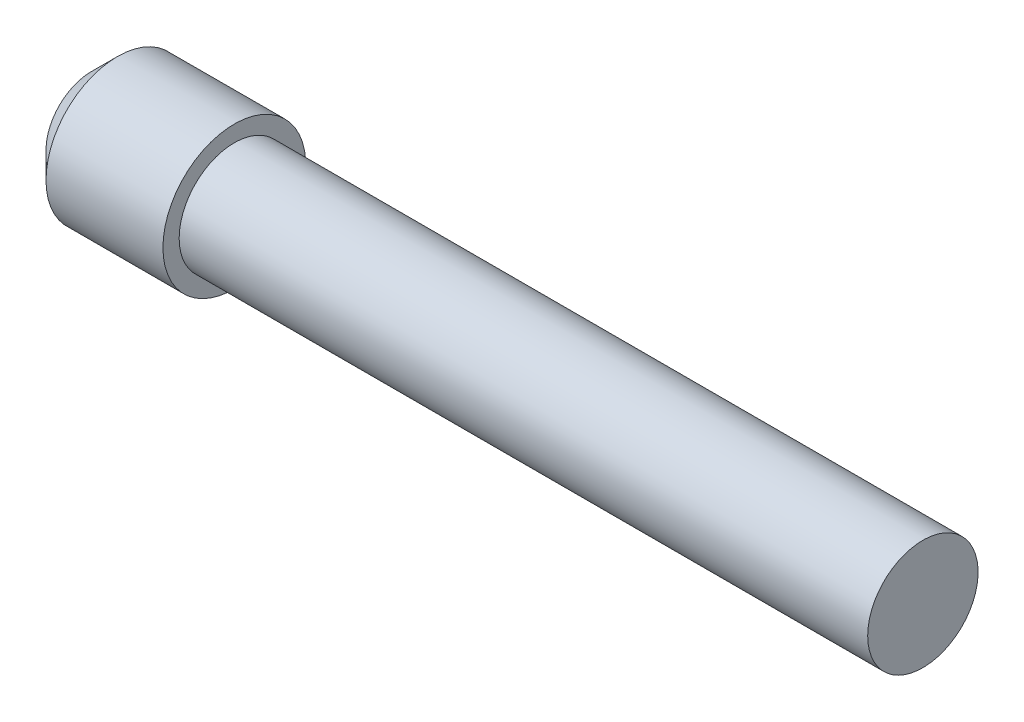
SolidWorks part; units mm, degrees
ref_plane "Front Plane" through (0, 0, 0) normal (0, 0, 1) x (1, 0, 0)
ref_plane "Top Plane" through (0, 0, 0) normal (0, 1, 0) x (1, 0, 0)
ref_plane "Right Plane" through (0, 0, 0) normal (1, 0, 0) x (0, 0, -1)
sketch "Sketch1" plane through (0, 0, 0) normal (0, 0, 1) x (1, 0, 0)
  line L0 (-9.4589, 0) -> (1.0894, 0) construction
  line L1 (0, 2.75) -> (-5.5, 2.75)
  line L2 (-5.5, 2.75) -> (-5.5, 0)
  line L3 (-5.5, 0) -> (26.5, 0)
  line L4 (0, 2.75) -> (0, 2.125)
  line L5 (0, 2.125) -> (0, 0) construction
  line L6 (0, 2.125) -> (26.5, 2.125)
  line L7 (26.5, 2.125) -> (26.5, 0)
  line L8 (9.5, 0) -> (9.5, 2.125) construction
  dimension "D1" = 9.5
  dimension "OD" = 5.5
  dimension "ID" = 4.25
  dimension "D2" = 17
  dimension "D3" = 5.5
revolve "Revolve1" add sketch "Sketch1" angle 360 about L0
chamfer "Chamfer1" distance 1 angle 45 1 edges at (-5.5, 0, 2.75)
